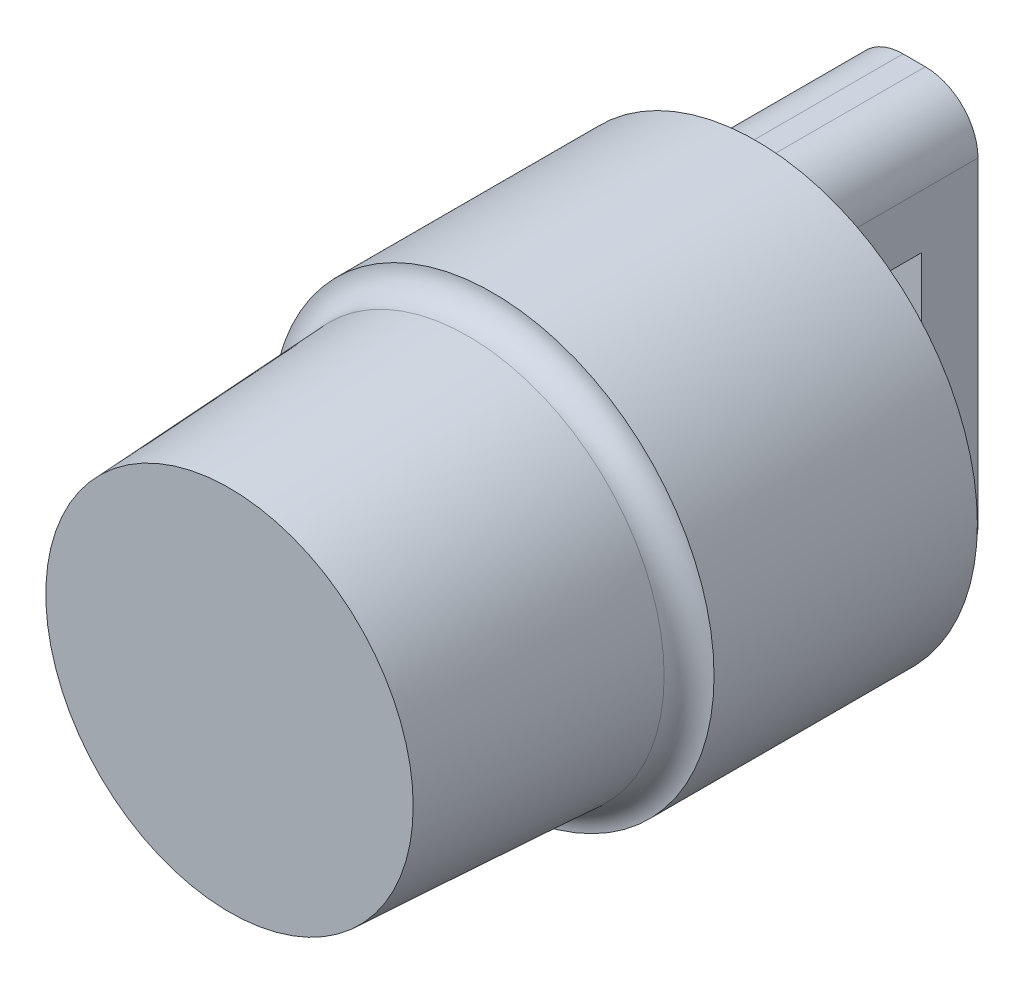
SolidWorks part; units mm, degrees
ref_plane "Спереди" through (0, 0, 0) normal (0, 0, 1) x (1, 0, 0)
ref_plane "Сверху" through (0, 0, 0) normal (0, 1, 0) x (1, 0, 0)
ref_plane "Справа" through (0, 0, 0) normal (1, 0, 0) x (0, 0, -1)
sketch "Эскиз1" plane through (0, 0, 0) normal (0, 0, 1) x (1, 0, 0)
  circle A0 centre (0, 0) radius 8.4
  dimension "D1" = 16.8
extrude "Бобышка-Вытянуть1" add sketch "Эскиз1" along normal blind 10
sketch "Эскиз2" plane through (0, 0, 10) normal (0, 0, 1) x (1, 0, 0)
  circle A0 centre (0, 0) radius 7.5
  dimension "D1" = 15
extrude "Бобышка-Вытянуть2" add sketch "Эскиз2" along normal blind 10 draft 3
sketch "Эскиз3" plane through (0, 0, 0) normal (0, 0, -1) x (-1, 0, 0)
  line L1 (-2.4231, 8.0429) -> (2.4231, 8.0429)
  line L2 (-2.4231, 8.0429) -> (-2.4231, -8.0429)
  line L3 (-2.4231, -8.0429) -> (2.4231, -8.0429)
  line L4 (2.4231, 8.0429) -> (2.4231, -8.0429)
  line L5 (-2.4231, 8.0429) -> (2.4231, -8.0429) construction
  line L6 (-2.4231, -8.0429) -> (2.4231, 8.0429) construction
  circle A0 centre (0, 0) radius 8.4 construction
  point P0 (0, 0)
extrude "Бобышка-Вытянуть3" add sketch "Эскиз3" along normal blind 6
fillet "Скругление1" radius 2 4 edges at (2.4231, -8.0429, -3) (-2.4231, -8.0429, -3) (-2.4231, 8.0429, -3) (2.4231, 8.0429, -3)
fillet "Скругление2" radius 1 1 edges at (7.5, 0, 10)
sketch "Эскиз4" plane through (-2.4231, 0, 0) normal (-1, 0, 0) x (0, 0, 1)
  line L1 (-3.8598, 4) -> (-1.8598, 4)
  line L2 (-3.8598, 4) -> (-3.8598, -4)
  line L3 (-3.8598, -4) -> (-1.8598, -4)
  line L4 (-1.8598, 4) -> (-1.8598, -4)
  line L5 (-3.8598, 4) -> (-1.8598, -4) construction
  line L6 (-3.8598, -4) -> (-1.8598, 4) construction
  point P0 (-2.8598, 0)
  point P5 (0, 0)
  dimension "D1" = 2
  dimension "D2" = 8
extrude "Вырез-Вытянуть1" cut sketch "Эскиз4" against normal through all
